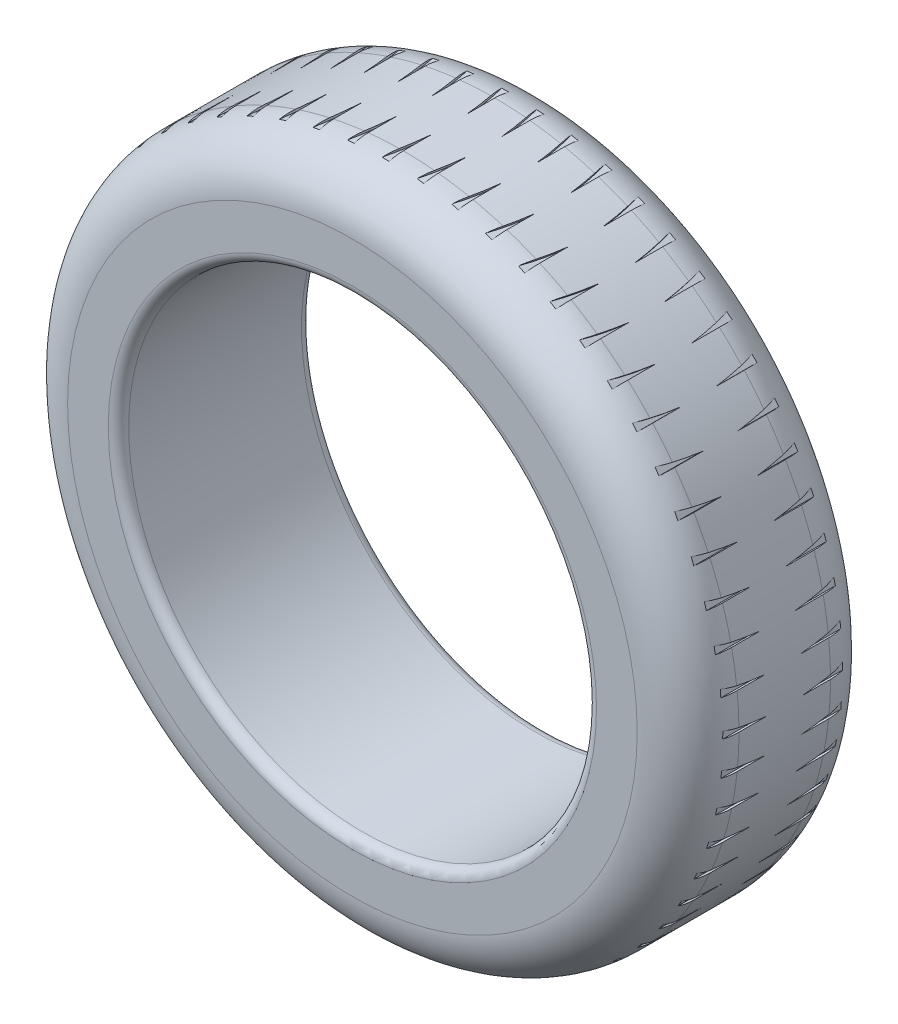
SolidWorks part; units mm, degrees
ref_plane "Front Plane" through (0, 0, 0) normal (0, 0, 1) x (1, 0, 0)
ref_plane "Top Plane" through (0, 0, 0) normal (0, 1, 0) x (1, 0, 0)
ref_plane "Right Plane" through (0, 0, 0) normal (1, 0, 0) x (0, 0, -1)
sketch "Sketch1" plane through (0, 0, 0) normal (0, 0, 1) x (1, 0, 0)
  circle A0 centre (0, 0) radius 230
  circle A1 centre (0, 0) radius 330
  dimension "D1" = 460
  dimension "D2" = 660
extrude "Boss-Extrude1" add sketch "Sketch1" against normal blind 190
fillet "Fillet4" radius 50 2 edges at (330, 0, -190) (330, 0, 0)
ref_plane "Plane1" through (0, 340, 0) normal (0, 1, 0) x (1, 0, 0)
sketch "Sketch2" plane through (0, 340, 0) normal (0, 1, 0) x (1, 0, 0)
  line L0 (0, 77.68) -> (0, 0)
  line L2 (0, 0) -> (-10, 0)
  line L3 (-10, 0) -> (-10, 25)
  spline S0 degree 3 poles (0, 77.68) (-1.474, 64.1927) (-3.5991, 46.6692) (-10, 25) knots 0 0 0 0 1 1 1 1
  dimension "D1" = 10
extrude "Cut-Extrude1" cut sketch "Sketch2" against normal blind 12
pattern_circular "CirPattern1" count 60 over 360 about axis through (0, 0, 0) along (0, 0, 1) of "Cut-Extrude1"
ref_plane "Plane2" through (0, 0, -95) normal (0, 0, 1) x (1, 0, 0)
mirror "Mirror1" about plane through (0, 0, -95) normal (0, 0, 1) of "CirPattern1"
fillet "Fillet5" radius 10 2 edges at (230, 0, -190) (230, 0, 0)
